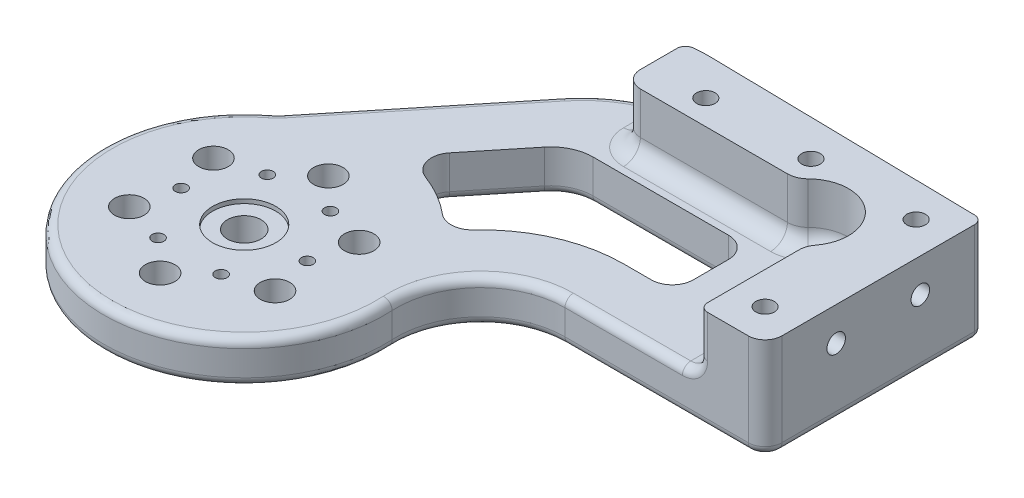
SolidWorks part; units mm, degrees
ref_plane "Front Plane" through (0, 0, 0) normal (0, 0, 1) x (1, 0, 0)
ref_plane "Top Plane" through (0, 0, 0) normal (0, 1, 0) x (1, 0, 0)
ref_plane "Right Plane" through (0, 0, 0) normal (1, 0, 0) x (0, 0, -1)
sketch "Sketch1" plane through (0, 0, 0) normal (0, 1, 0) x (1, 0, 0)
  line L0 (-17.1769, -49.3654) -> (46.2562, -49.3654)
  line L1 (47.6308, 2.0885) -> (-35.4788, 3.5633)
  line L2 (-59.3233, -7.5496) -> (-89.0679, -44.2724)
  line L3 (-41.2685, -46.3654) -> (-0.2685, -46.3654)
  line L4 (-42.2685, -45.3654) -> (-42.2685, -4.3654)
  line L5 (-41.2685, -3.3654) -> (-0.2685, -3.3654)
  line L6 (-0.2685, -46.3654) -> (18.7315, -46.3654)
  line L7 (19.7315, -45.3654) -> (19.7315, -4.3654)
  line L8 (18.7315, -3.3654) -> (-0.2685, -3.3654)
  arc A0 (-101.2312, -59.5483) -> (-37.1453, -70.49) centre (-70.4425, -72.3654) ccw
  arc A1 (-17.1769, -49.3654) -> (-37.1453, -70.49) centre (-17.1769, -69.3654) ccw
  arc A2 (-90.7495, -45.9107) -> (-37.1453, -70.49) centre (-70.4425, -72.3654) ccw
  circle A3 centre (-70.4425, -72.3654) radius 4
  arc A4 (-90.7495, -45.9107) -> (-89.0679, -44.2724) centre (-96.8386, -37.9783) ccw
  arc A5 (-35.4788, 3.5633) -> (-59.3233, -7.5496) centre (-36.0111, -26.4319) ccw
  arc A6 (-41.2685, -46.3654) -> (-42.2685, -45.3654) centre (-41.2685, -45.3654) cw
  arc A7 (-41.2685, -3.3654) -> (-42.2685, -4.3654) centre (-41.2685, -4.3654) ccw
  arc A8 (19.7315, -45.3654) -> (18.7315, -46.3654) centre (18.7315, -45.3654) cw
  arc A9 (18.7315, -3.3654) -> (19.7315, -4.3654) centre (18.7315, -4.3654) cw
  arc A10 (64.8139, -55.7939) -> (65.9036, 7.8913) centre (89.5575, -24.3654) ccw
  arc A11 (46.2562, -49.3654) -> (64.8139, -55.7939) centre (46.2562, -79.3654) cw
  arc A12 (65.9036, 7.8913) -> (47.6308, 2.0885) centre (48.1631, 32.0838) cw
  circle A13 centre (89.5575, -24.8654) radius 7
  point P12 (-21.2685, -24.8654)
  dimension "D1" = 20
  dimension "D2" = 10
  dimension "D3" = 30
  dimension "D4" = 1
  dimension "D5" = 1
  dimension "D6" = 1
  dimension "D7" = 1
  dimension "D8" = 30
  dimension "D9" = 30
extrude "Boss-Extrude1" add sketch "Sketch1" along normal blind 10 contours A10 A12 L1 A5 L2 A4 A2 A0 A1 L0 A11 A13 L8 A9 L7 A8 L6 L3 A6 L4 A7 L5 A3
sketch "Sketch2" plane through (0, 10, 0) normal (0, 1, 0) x (1, 0, 0)
  line L22 (19.7315, -49.3654) -> (14.7315, -49.3654)
  line L23 (14.7315, -49.3654) -> (14.7315, -25.694)
  line L24 (30.4027, -49.3654) -> (19.7315, -49.3654)
  line L26 (19.7315, -45.3654) -> (19.7315, -4.3654) construction
  line L28 (47.6308, 2.0885) -> (-35.4788, 3.5633) construction
  line L29 (19.7315, 2.5836) -> (30.4027, 2.3942)
  line L30 (30.4027, 2.3942) -> (30.4027, -49.3654)
  line L31 (-17.1769, -49.3654) -> (46.2562, -49.3654) construction
  line L33 (-35.4788, 3.5633) -> (19.7315, 2.5836)
  line L34 (-41.2685, 3.1038) -> (-41.2685, -11.3473)
  line L37 (-41.2685, -11.3473) -> (-2.3084, -11.3473)
  arc A8 (-35.4788, 3.5633) -> (-59.3233, -7.5496) centre (-36.0111, -26.4319) ccw construction
  arc A9 (-35.4788, 3.5633) -> (-41.2685, 3.1038) centre (-36.0111, -26.4319) ccw
  arc A14 (15.7417, -22.6805) -> (1.1968, -9.9129) centre (7.9991, -16.8323) ccw
  arc A15 (1.1968, -9.9129) -> (-2.3084, -11.3473) centre (-2.3084, -6.3473) cw
  arc A16 (15.7417, -22.6805) -> (14.7315, -25.694) centre (19.7315, -25.694) ccw
  point P20 (19.7315, -24.8654)
  dimension "D1" = 5
  dimension "D2" = 5
extrude "Boss-Extrude3" add sketch "Sketch2" along normal blind 14
sketch "Sketch4" plane through (0, 10, 0) normal (0, 1, 0) x (1, 0, 0)
  line L1 (30.4027, -97.3186) -> (150.9693, -97.3186)
  line L2 (30.4027, -97.3186) -> (30.4027, 45.96)
  line L3 (30.4027, 45.96) -> (150.9693, 45.96)
  line L4 (150.9693, -97.3186) -> (150.9693, 45.96)
extrude "Cut-Extrude1" cut sketch "Sketch4" against normal blind 14
sketch "Sketch5" plane through (0, 10, 0) normal (0, 1, 0) x (1, 0, 0)
  circle A1 centre (-87.763, -62.3654) radius 3.5
  circle A2 centre (-70.4425, -52.3654) radius 3.5
  circle A3 centre (-53.122, -62.3654) radius 3.5
  circle A4 centre (-53.122, -82.3654) radius 3.5
  circle A5 centre (-70.4425, -92.3654) radius 3.5
  circle A6 centre (-87.763, -82.3654) radius 3.5
  circle A8 centre (-77.9425, -59.375) radius 1.4
  circle A9 centre (-62.9425, -59.375) radius 1.4
  circle A10 centre (-55.4425, -72.3654) radius 1.4
  circle A11 centre (-62.9425, -85.3557) radius 1.4
  circle A12 centre (-77.9425, -85.3557) radius 1.4
  circle A13 centre (-85.4425, -72.3654) radius 1.4
  point P17 (-70.4425, -72.3654)
  point P29 (-70.4425, -72.3654)
  dimension "D1" = 6
  dimension "D2" = 6
extrude "Cut-Extrude2" cut sketch "Sketch5" against normal blind 10 contours A2 | A1 | A6 | A5 | A4 | A3 | A11 | A10 | A12 | A13 | A8 | A9
sketch "Sketch6" plane through (0, 10, 0) normal (0, 1, 0) x (1, 0, 0)
  line L0 (-42.8981, -16.9908) -> (-10.6672, -16.9908)
  line L1 (-89.0679, -44.2724) -> (-59.3233, -7.5496)
  line L2 (-60.8058, -33.2117) -> (-50.6689, -20.6967)
  line L3 (-5.6672, -21.9908) -> (-5.6672, -30.3654)
  line L4 (-10.6672, -35.3654) -> (-17.1769, -35.3654)
  line L6 (-77.4118, -53.7136) -> (-47.6672, -16.9908) construction
  arc A1 (-17.1769, -35.3654) -> (-42.1118, -46.2515) centre (-17.1769, -69.3654) ccw
  arc A2 (-48.985, -46.689) -> (-58.6783, -41.0396) centre (-70.4425, -72.3654) ccw
  arc A4 (-42.8981, -16.9908) -> (-50.6689, -20.6967) centre (-42.8981, -26.9908) ccw
  arc A5 (-5.6672, -21.9908) -> (-10.6672, -16.9908) centre (-10.6672, -21.9908) ccw
  arc A6 (-5.6672, -30.3654) -> (-10.6672, -35.3654) centre (-10.6672, -30.3654) cw
  arc A7 (-48.985, -46.689) -> (-42.1118, -46.2515) centre (-45.7787, -42.8524) ccw
  arc A8 (-60.8058, -33.2117) -> (-58.6783, -41.0396) centre (-56.9204, -36.3588) ccw
  dimension "D2" = 10
  dimension "D3" = 5
  dimension "D4" = 5
  dimension "D5" = 5
  dimension "D6" = 5
  dimension "D1" = 15
extrude "Cut-Extrude3" cut sketch "Sketch6" against normal blind 25 contours L2 A8 A2 A7 A1 L4 A6 L3 A5 L0 A4
sketch "Sketch7" plane through (0, 10, 0) normal (0, 1, 0) x (1, 0, 0)
  circle A0 centre (-70.4425, -72.3654) radius 7.5
extrude "Cut-Extrude4" cut sketch "Sketch7" against normal blind 1
sketch "Sketch8" plane through (0, 24, 0) normal (0, 1, 0) x (1, 0, 0)
  circle A0 centre (22.4027, -41.3654) radius 2.2
  circle A1 centre (22.4027, -5.4638) radius 2.2
  circle A2 centre (-27.5973, -5.4638) radius 2.2
  circle A3 centre (-2.5973, -5.4638) radius 2.2
extrude "Cut-Extrude5" cut sketch "Sketch8" against normal blind 46
sketch "Sketch9" plane through (0, 0, 0) normal (0, -1, 0) x (1, 0, 0)
  circle A0 centre (-27.5973, 5.4638) radius 3.5
  circle A1 centre (-2.5973, 5.4638) radius 3.5
  circle A2 centre (22.4027, 5.4638) radius 3.5
  circle A3 centre (22.4027, 41.3654) radius 3.5
extrude "Cut-Extrude6" cut sketch "Sketch9" against normal blind 12
fillet "Fillet1" radius 2 36 edges at (-47.2027, 0, 17.9647) (-26.7827, 0, 16.9908) (-7.1317, 0, 18.4553) (-5.6672, 0, 26.1781) (-7.1317, 0, 33.9009) (-13.9221, 0, 35.3654) (-30.7807, 0, 38.2055) (-45.461, 0, 47.8423) (-53.5931, 0, 43.4552) (-61.7454, 0, 37.6702) (-55.7373, 0, 26.9542) (-70.4425, 0, 55.8654) (-62.9425, 0, 60.775) (-77.9425, 0, 60.775) (-85.4425, 0, 73.7654) (-87.763, 0, 65.8654) (-87.763, 0, 85.8654) (-70.4425, 0, 95.8654) (-53.122, 0, 85.8654) (-77.9425, 0, 86.7557) (-55.4425, 0, 73.7654) (-62.9425, 0, 86.7557) (-53.122, 0, 65.8654) (-70.4425, 0, 76.3654) (-48.6841, 0, -0.7599) (-74.1956, 0, 25.911) (-89.8605, 0, 45.1411) (-84.3429, 0, 102.6804) (-31.7112, 0, 55.6266) (6.6129, 0, 49.3654) (30.4027, 0, 23.4856) (-2.5381, 0, -2.9788) (22.4027, 0, 37.8654) (22.4027, 0, 1.9638) (-2.5973, 0, 1.9638) (-27.5973, 0, 1.9638)
fillet "Fillet2" radius 4 3 edges at (29.8169, 0.5858, 48.7796) (30.4027, 13, 49.3654) (-41.2685, 17, 11.3473)
fillet "Fillet3" radius 4 7 edges at (-41.2685, 10, 2.1217) (-40.0969, 10, 10.1757) (-0.4147, 10, 10.9748) (-19.7884, 10, 11.3473) (14.7315, 10, 37.5297) (14.4002, 10, 9.5401) (14.9908, 10, 24.1048)
fillet "Fillet4" radius 2 10 edges at (14.7315, 19, 49.3654) (13.56, 11.1716, 49.3654) (-3.2227, 10, 49.3654) (-31.7112, 10, 55.6266) (-84.3429, 10, 102.6804) (-89.8605, 10, 45.1411) (-74.1956, 10, 25.911) (-52.9962, 10, 1.7033) (-42.7204, 10.9166, -2.8082) (-41.2685, 19, -3.1038)
fillet "Fillet5" radius 2 2 edges at (29.8169, 0.5858, -1.8187) (30.4027, 13, -2.3942)
sketch "Sketch10" plane through (30.4027, 0, 0) normal (1, 0, 0) x (0, 0, -1)
  circle A1 centre (-32.468, 16) radius 2.2
  circle A2 centre (-12.468, 16) radius 2.2
extrude "Cut-Extrude7" cut sketch "Sketch10" against normal blind 23
